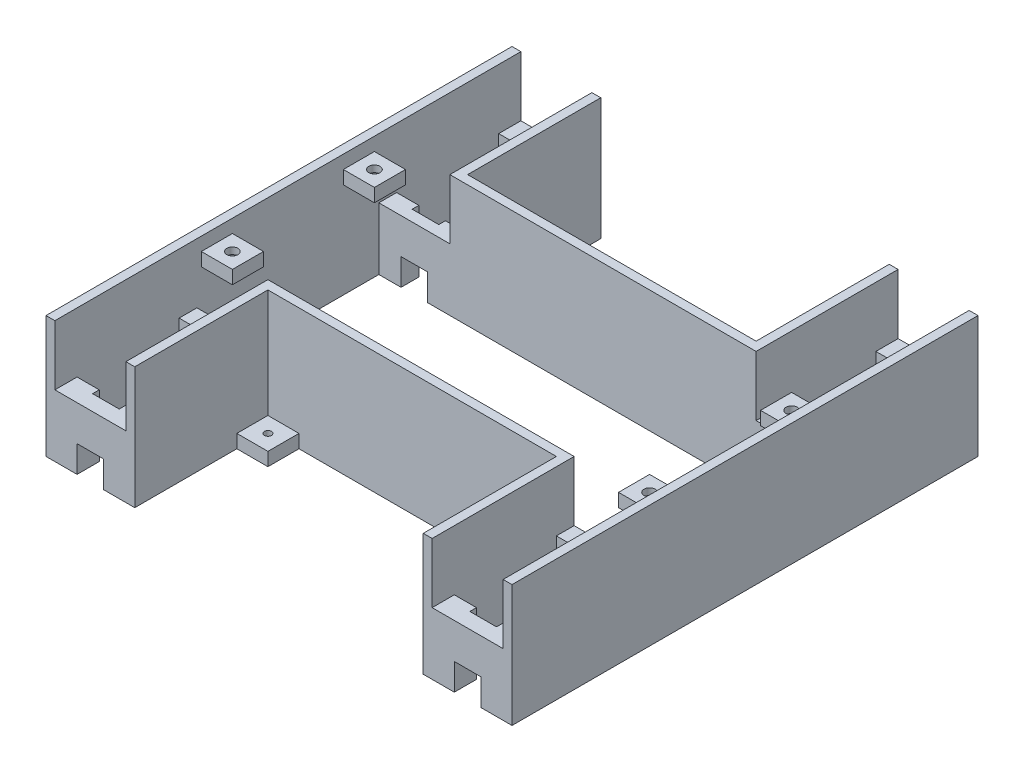
SolidWorks part; units mm, degrees
ref_plane "前视基准面" through (0, 0, 0) normal (0, 0, 1) x (1, 0, 0)
ref_plane "上视基准面" through (0, 0, 0) normal (0, 1, 0) x (1, 0, 0)
ref_plane "右视基准面" through (0, 0, 0) normal (1, 0, 0) x (0, 0, -1)
other "Configuration Table"
sketch "草图1" plane through (0, 0, 0) normal (0, 1, 0) x (1, 0, 0)
  line L1 (0, 20.5) -> (101, 20.5)
  line L2 (0, 20.5) -> (0, -20.5)
  line L3 (0, -20.5) -> (101, -20.5)
  line L4 (101, 20.5) -> (101, -20.5)
  line L5 (0, 52.5) -> (16, 52.5)
  line L6 (0, 52.5) -> (0, 20.5)
  line L7 (0, 20.5) -> (16, 20.5)
  line L8 (16, 52.5) -> (16, 20.5)
  line L9 (101, 20.5) -> (85, 20.5)
  line L10 (101, 20.5) -> (101, 52.5)
  line L11 (101, 52.5) -> (85, 52.5)
  line L12 (85, 20.5) -> (85, 52.5)
  line L13 (101, -52.5) -> (85, -52.5)
  line L14 (101, -52.5) -> (101, -20.5)
  line L15 (101, -20.5) -> (85, -20.5)
  line L16 (85, -52.5) -> (85, -20.5)
  line L17 (0, -20.5) -> (16, -20.5)
  line L18 (0, -20.5) -> (0, -52.5)
  line L19 (0, -52.5) -> (16, -52.5)
  line L20 (16, -20.5) -> (16, -52.5)
  line L21 (0, 52.5) -> (-2, 52.5)
  line L22 (0, 52.5) -> (0, -52.5)
  line L23 (0, -52.5) -> (-2, -52.5)
  line L24 (-2, 52.5) -> (-2, -52.5)
  line L25 (101, 52.5) -> (103, 52.5)
  line L26 (101, 52.5) -> (101, -52.5)
  line L27 (101, -52.5) -> (103, -52.5)
  line L28 (103, 52.5) -> (103, -52.5)
  line L29 (103, 52.5) -> (83, 52.5)
  line L30 (103, 52.5) -> (103, 54.5)
  line L31 (103, 54.5) -> (83, 54.5)
  line L32 (83, 52.5) -> (83, 54.5)
  line L33 (103, -52.5) -> (83, -52.5)
  line L34 (103, -52.5) -> (103, -54.5)
  line L35 (103, -54.5) -> (83, -54.5)
  line L36 (83, -52.5) -> (83, -54.5)
  line L37 (-2, 52.5) -> (18, 52.5)
  line L38 (-2, 52.5) -> (-2, 54.5)
  line L39 (-2, 54.5) -> (18, 54.5)
  line L40 (18, 52.5) -> (18, 54.5)
  line L41 (-2, -52.5) -> (18, -52.5)
  line L42 (-2, -52.5) -> (-2, -54.5)
  line L43 (-2, -54.5) -> (18, -54.5)
  line L44 (18, -52.5) -> (18, -54.5)
  line L45 (18, 52.5) -> (16, 52.5)
  line L46 (18, 52.5) -> (18, 20.5)
  line L47 (18, 20.5) -> (16, 20.5)
  line L48 (16, 52.5) -> (16, 20.5)
  line L49 (83, 52.5) -> (85, 52.5)
  line L50 (83, 52.5) -> (83, 20.5)
  line L51 (83, 20.5) -> (85, 20.5)
  line L52 (85, 52.5) -> (85, 20.5)
  line L53 (18, -52.5) -> (16, -52.5)
  line L54 (18, -52.5) -> (18, -20.5)
  line L55 (18, -20.5) -> (16, -20.5)
  line L56 (16, -52.5) -> (16, -20.5)
  line L57 (83, -52.5) -> (85, -52.5)
  line L58 (83, -52.5) -> (83, -20.5)
  line L59 (83, -20.5) -> (85, -20.5)
  line L60 (85, -52.5) -> (85, -20.5)
  line L61 (18, -20.5) -> (83, -20.5)
  line L62 (18, -20.5) -> (18, -22.5)
  line L63 (18, -22.5) -> (83, -22.5)
  line L64 (83, -20.5) -> (83, -22.5)
  line L65 (18, 20.5) -> (83, 20.5)
  line L66 (18, 20.5) -> (18, 22.5)
  line L67 (18, 22.5) -> (83, 22.5)
  line L68 (83, 20.5) -> (83, 22.5)
  point P4 (0, 0)
  dimension "D1" = 101
  dimension "D2" = 41
  dimension "D3" = 32
  dimension "D4" = 16
  dimension "D6" = 2
extrude "凸台-拉伸2" add sketch "草图1" along normal blind 27.5 contours L21 L24 L23 L18 L2 L6 | L37 L40 L39 L38 L21 L5 | L46 L37 L8 L1 | L67 L46 L1 L50 | L29 L50 L1 L12 | L32 L29 L11 L25 L30 L31 | L28 L25 L10 L4 L14 L27 | L33 L36 L35 L34 L27 L13 | L58 L33 L16 L3 | L54 L63 L58 L3 | L41 L54 L3 L20 | L44 L41 L19 L23 L42 L43 region at (-1, 0, 0) region at (17, 0, -36.5) region at (8, 0, -53.5) region at (50.5, 0, -21.5) region at (17, 0, 36.5) region at (8, 0, 53.5) region at (84, 0, -36.5) region at (50.5, 0, 21.5) region at (84, 0, 36.5) region at (102, 0, 0) region at (93, 0, -53.5) region at (93, 0, 53.5)
sketch "草图2" plane through (0, 0, 0) normal (0, -1, 0) x (1, 0, 0)
  line L0 (0, -52.5) -> (0, 52.5) construction
  line L1 (16, 52.5) -> (0, 52.5)
  line L2 (16, 52.5) -> (16, 47.5)
  line L3 (16, 47.5) -> (0, 47.5)
  line L4 (0, 52.5) -> (0, 47.5)
  line L5 (103, -54.5) -> (103, 54.5) construction
  line L6 (-2, 54.5) -> (103, 54.5)
  line L7 (-2, 54.5) -> (-2, 52.5)
  line L8 (-2, 52.5) -> (103, 52.5)
  line L9 (103, 54.5) -> (103, 52.5)
  line L10 (101, 52.5) -> (101, -52.5) construction
  line L11 (85, 52.5) -> (101, 52.5)
  line L12 (85, 52.5) -> (85, 47.5)
  line L13 (85, 47.5) -> (101, 47.5)
  line L14 (101, 52.5) -> (101, 47.5)
  line L16 (16, -52.5) -> (0, -52.5)
  line L17 (16, -52.5) -> (16, -47.5)
  line L18 (16, -47.5) -> (0, -47.5)
  line L19 (0, -52.5) -> (0, -47.5)
  line L20 (85, -52.5) -> (101, -52.5)
  line L21 (85, -52.5) -> (85, -47.5)
  line L22 (85, -47.5) -> (101, -47.5)
  line L23 (101, -52.5) -> (101, -47.5)
  line L24 (-2, -54.5) -> (103, -54.5)
  line L25 (-2, -54.5) -> (-2, -52.5)
  line L26 (-2, -52.5) -> (103, -52.5)
  line L27 (103, -54.5) -> (103, -52.5)
  line L28 (16, 20.5) -> (0, 20.5)
  line L29 (16, 20.5) -> (16, 24.5)
  line L30 (16, 24.5) -> (0, 24.5)
  line L31 (0, 20.5) -> (0, 24.5)
  line L32 (85, 20.5) -> (101, 20.5)
  line L33 (85, 20.5) -> (85, 24.5)
  line L34 (85, 24.5) -> (101, 24.5)
  line L35 (101, 20.5) -> (101, 24.5)
  line L36 (85, -20.5) -> (101, -20.5)
  line L37 (85, -20.5) -> (85, -24.5)
  line L38 (85, -24.5) -> (101, -24.5)
  line L39 (101, -20.5) -> (101, -24.5)
  line L40 (16, -20.5) -> (0, -20.5)
  line L41 (16, -20.5) -> (16, -24.5)
  line L42 (16, -24.5) -> (0, -24.5)
  line L43 (0, -20.5) -> (0, -24.5)
  dimension "D1" = 5
  dimension "D2" = 4
extrude "凸台-拉伸3" add sketch "草图2" against normal blind 14 contours L13 L14 L11 L12 | L3 L4 L1 L2 | L16 L19 L18 L17 | L20 L23 L22 L21 | L28 L31 L30 L29 | L32 L35 L34 L33 | L42 L43 L40 L41 | L38 L39 L36 L37
extrude "切除-拉伸1" cut sketch "草图2<3>" against normal through all contours L24 L27 L26 L25 | L6 L9 L8 L7
sketch "草图2<3>" plane through (0, 0, 0) normal (0, -1, 0) x (1, 0, 0) same geometry as "草图2"
sketch "草图3" plane through (0, 0, 0) normal (0, -1, 0) x (1, 0, 0)
  line L0 (101, 20.5) -> (101, -20.5) construction
  line L1 (0, 19.5) -> (7, 19.5)
  line L2 (0, 19.5) -> (0, 12.5)
  line L3 (0, 12.5) -> (7, 12.5)
  line L4 (7, 19.5) -> (7, 12.5)
  line L5 (0, -19.5) -> (7, -19.5)
  line L6 (0, -19.5) -> (0, -12.5)
  line L7 (0, -12.5) -> (7, -12.5)
  line L8 (7, -19.5) -> (7, -12.5)
  line L9 (101, 19.5) -> (94, 19.5)
  line L10 (101, 19.5) -> (101, 12.5)
  line L11 (101, 12.5) -> (94, 12.5)
  line L12 (94, 19.5) -> (94, 12.5)
  line L13 (101, -19.5) -> (94, -19.5)
  line L14 (101, -19.5) -> (101, -12.5)
  line L15 (101, -12.5) -> (94, -12.5)
  line L16 (94, -19.5) -> (94, -12.5)
  line L17 (0, -20.5) -> (0, 20.5) construction
  line L18 (0, 20.5) -> (101, 20.5) construction
  line L19 (0, -20.5) -> (101, -20.5) construction
  line L20 (0, 19.5) -> (7, 12.5) construction
  line L21 (0, -12.5) -> (7, -19.5) construction
  line L22 (94, -12.5) -> (101, -19.5) construction
  line L23 (94, 19.5) -> (101, 12.5) construction
  circle A0 centre (3.5, 16) radius 2
  circle A1 centre (3.5, 16) radius 1.25
  circle A2 centre (97.5, 16) radius 2
  circle A3 centre (97.5, 16) radius 1.25
  circle A4 centre (97.5, -16) radius 2
  circle A5 centre (97.5, -16) radius 1.25
  circle A8 centre (3.5, -16) radius 1.25
  circle A9 centre (3.5, -16) radius 2
  dimension "D4" = 2.5
  dimension "D5" = 4
  dimension "D1" = 7
  dimension "D2" = 1
  dimension "D3" = 1
extrude "凸台-拉伸4" add sketch "草图3" along normal blind 3 from offset 24.5 separate body contours L8 L7 L6 L5 | L4 L3 L2 L1 | L12 L11 L10 L9 | L15 L16 L13 L14 | A1 | A3 | A5 | A8 offset against normal yes
extrude "切除-拉伸3" cut sketch "草图3<4>" against normal blind 1.5 from surface contours A0 | A9 | A2 | A4 starting at face at (3.5, 21.5, 16)
sketch "草图3<4>" plane through (0, 0, 0) normal (0, -1, 0) x (1, 0, 0) same geometry as "草图3"
sketch "草图4" plane through (0, 0, 0) normal (0, -1, 0) x (1, 0, 0)
  line L0 (18, 22.5) -> (83, 22.5) construction
  line L1 (18, 29.5) -> (25, 29.5)
  line L2 (18, 29.5) -> (18, 22.5)
  line L3 (18, 22.5) -> (25, 22.5)
  line L4 (25, 29.5) -> (25, 22.5)
  line L5 (18, -22.5) -> (83, -22.5) construction
  line L6 (83, 29.5) -> (76, 29.5)
  line L7 (83, 29.5) -> (83, 22.5)
  line L8 (83, 22.5) -> (76, 22.5)
  line L9 (76, 29.5) -> (76, 22.5)
  line L10 (18, -29.5) -> (25, -29.5)
  line L11 (18, -29.5) -> (18, -22.5)
  line L12 (18, -22.5) -> (25, -22.5)
  line L13 (25, -29.5) -> (25, -22.5)
  line L15 (83, -29.5) -> (76, -29.5)
  line L16 (83, -29.5) -> (83, -22.5)
  line L17 (83, -22.5) -> (76, -22.5)
  line L18 (76, -29.5) -> (76, -22.5)
  line L19 (18, -22.5) -> (18, -52.5) construction
  line L20 (83, 52.5) -> (83, 22.5) construction
  line L21 (18, 29.5) -> (25, 22.5) construction
  line L22 (83, 29.5) -> (76, 22.5) construction
  line L23 (25, -29.5) -> (18, -22.5) construction
  line L24 (83, -29.5) -> (76, -22.5) construction
  circle A0 centre (21.5, 26) radius 0.8
  circle A1 centre (79.5, 26) radius 0.8
  circle A2 centre (79.5, -26) radius 0.8
  circle A3 centre (21.5, -26) radius 0.8
  dimension "D1" = 1.6
  dimension "D2" = 7
  dimension "D3" = 7
extrude "凸台-拉伸5" add sketch "草图4" against normal blind 3 separate body contours L10 L13 L12 L11 | A3 | L1 L4 L3 L2 | A0 | L6 L9 L8 L7 | A1 | L15 L18 L17 L16 | A2
sketch "草图5" plane through (0, 0, 52.5) normal (0, 0, 1) x (1, 0, 0)
  line L5 (-2, 0) -> (18, 0) construction
  line L6 (5, 0) -> (11, 0)
  line L7 (5, 0) -> (5, 6)
  line L8 (5, 6) -> (11, 6)
  line L9 (11, 0) -> (11, 6)
  line L10 (83, 0) -> (103, 0) construction
  line L11 (90, 0) -> (96, 0)
  line L12 (90, 0) -> (90, 6)
  line L13 (90, 6) -> (96, 6)
  line L14 (96, 0) -> (96, 6)
  line L15 (-2, 27.5) -> (-2, 0) construction
  line L16 (18, 0) -> (18, 27.5) construction
  line L17 (83, 27.5) -> (83, 0) construction
  line L18 (103, 27.5) -> (103, 0) construction
  dimension "D1" = 7
  dimension "D2" = 7
  dimension "D3" = 7
  dimension "D4" = 7
  dimension "D5" = 6
extrude "切除-拉伸4" cut sketch "草图5" against normal through all
sketch "草图6" plane through (0, 6, 0) normal (0, -1, 0) x (1, 0, 0)
  line L0 (5, 47.5) -> (5, 52.5) construction
  line L1 (5, 49) -> (11, 49)
  line L2 (5, 49) -> (5, 47.5)
  line L3 (5, 47.5) -> (11, 47.5)
  line L4 (11, 49) -> (11, 47.5)
  line L6 (5, 20.5) -> (5, 24.5) construction
  line L7 (5, 24.5) -> (11, 24.5)
  line L8 (5, 24.5) -> (5, 23)
  line L9 (5, 23) -> (11, 23)
  line L10 (11, 24.5) -> (11, 23)
  line L11 (11, 24.5) -> (5, 24.5) construction
  line L13 (11, 20.5) -> (11, 24.5) construction
  line L14 (96, 20.5) -> (96, 24.5) construction
  line L15 (90, 24.5) -> (96, 24.5)
  line L16 (90, 24.5) -> (90, 23)
  line L17 (90, 23) -> (96, 23)
  line L18 (96, 24.5) -> (96, 23)
  line L19 (96, 47.5) -> (96, 52.5) construction
  line L20 (90, 47.5) -> (96, 47.5)
  line L21 (90, 47.5) -> (90, 49)
  line L22 (90, 49) -> (96, 49)
  line L23 (96, 47.5) -> (96, 49)
  line L24 (96, -24.5) -> (96, -20.5) construction
  line L25 (90, -24.5) -> (96, -24.5)
  line L26 (90, -24.5) -> (90, -23)
  line L27 (90, -23) -> (96, -23)
  line L28 (96, -24.5) -> (96, -23)
  line L29 (96, -52.5) -> (96, -47.5) construction
  line L30 (90, -47.5) -> (96, -47.5)
  line L31 (90, -47.5) -> (90, -49)
  line L32 (90, -49) -> (96, -49)
  line L33 (96, -47.5) -> (96, -49)
  line L34 (5, -52.5) -> (5, -47.5) construction
  line L35 (11, -47.5) -> (5, -47.5)
  line L36 (11, -47.5) -> (11, -49)
  line L37 (11, -49) -> (5, -49)
  line L38 (5, -47.5) -> (5, -49)
  line L39 (11, -24.5) -> (11, -20.5) construction
  line L40 (5, -24.5) -> (11, -24.5)
  line L41 (5, -24.5) -> (5, -23)
  line L42 (5, -23) -> (11, -23)
  line L43 (11, -24.5) -> (11, -23)
  dimension "D1" = 1.5
extrude "切除-拉伸5" cut sketch "草图6" against normal through all contours L3 L4 L1 L2 | L9 L10 L7 L8 | L40 L43 L42 L41 | L37 L38 L35 L36 | L32 L33 L30 L31 | L25 L28 L27 L26 | L17 L18 L15 L16 | L20 L23 L22 L21
